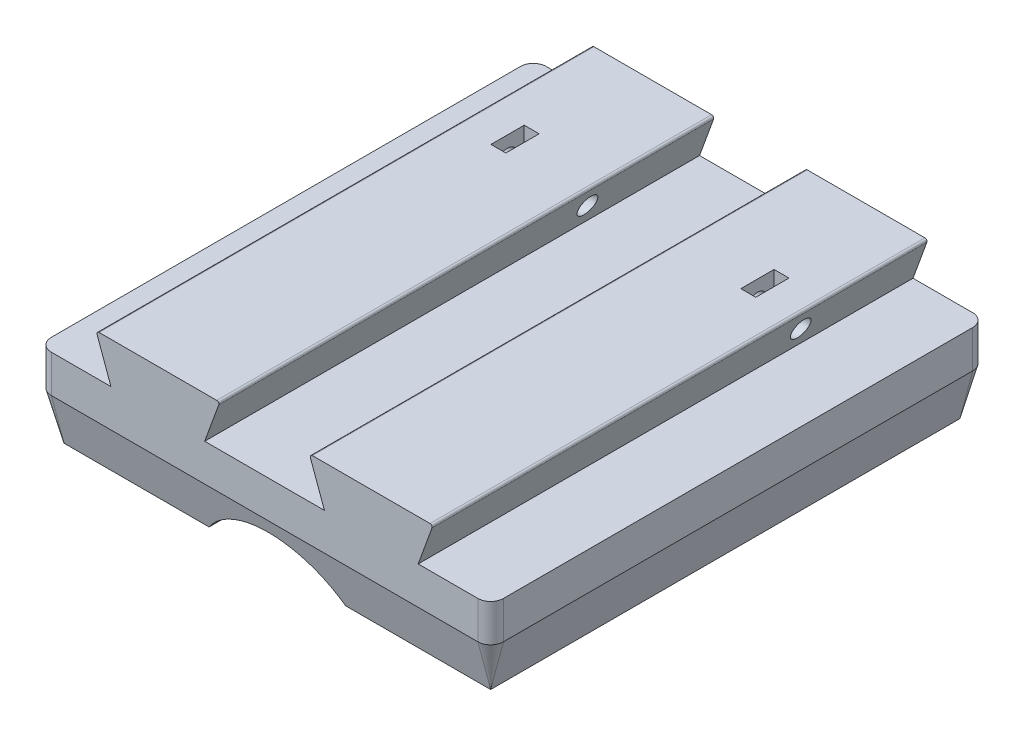
SolidWorks part; units mm, degrees
ref_plane "Front Plane" through (0, 0, 0) normal (0, 0, 1) x (1, 0, 0)
ref_plane "Top Plane" through (0, 0, 0) normal (0, 1, 0) x (1, 0, 0)
ref_plane "Right Plane" through (0, 0, 0) normal (1, 0, 0) x (0, 0, -1)
sketch "Sketch2" plane through (0, 0, 0) normal (0, 0, 1) x (1, 0, 0)
  line L0 (-39.5, -5.2867) -> (-10.5, -5.2867)
  line L1 (-10.5, -5.2867) -> (-14.0354, -15)
  line L2 (-14.0354, -15) -> (14.0354, -15)
  line L4 (-36.0059, -14.8867) -> (-39.5, -5.2867)
  line L5 (0, -16.28) -> (0, 16.28) construction
  line L10 (-36.0059, -14.8867) -> (-53, -14.8867)
  line L11 (-53, -14.8867) -> (-53, -34.8867)
  line L12 (-53, -34.8867) -> (-16, -34.8867)
  line L13 (39.5, -5.2867) -> (10.5, -5.2867)
  line L14 (10.5, -5.2867) -> (14.0354, -15)
  line L15 (53, -34.8867) -> (16, -34.8867)
  line L16 (53, -14.8867) -> (53, -34.8867)
  line L17 (36.0059, -14.8867) -> (53, -14.8867)
  line L18 (36.0059, -14.8867) -> (39.5, -5.2867)
  arc A0 (16, -34.8867) -> (-16, -34.8867) centre (0, -46.8867) ccw
  point P7 (-25, -5.2867)
  point P16 (0, -15)
  dimension "D5" = 40
  dimension "D1" = 25
  dimension "D2" = 29
  dimension "D3" = 20
  dimension "D4" = 12
  dimension "D6" = 53
  dimension "D7" = 70
  dimension "D8" = 70
  dimension "D9" = 9.6
extrude "Boss-Extrude1" add sketch "Sketch2" along normal blind 116 contours L15 A0 L12 L11 L10 L4 L0 L1 L2 L14 L13 L18 L17 L16
fillet "Fillet1" radius 3 4 edges at (53, -24.8867, 116) (-53, -24.8867, 116) (-53, -24.8867, 0) (53, -24.8867, 0)
chamfer "Chamfer2" distance 3 angle 75 5 edges at (52.1213, -34.8867, 0.8787) (-33, -34.8867, 0) (-52.1213, -34.8867, 115.1213) (-53, -34.8867, 58) (33, -34.8867, 116) tangent propagation no first distance on face at (39.8738, -34.8867, 58) first distance on face at (-39.8738, -34.8867, 58)
fillet "Fillet2" radius 0.5 4 edges at (-39.5, -5.2867, 58) (-10.5, -5.2867, 58) (10.5, -5.2867, 58) (39.5, -5.2867, 58)
sketch "Sketch3" plane through (0, -5.2867, 0) normal (0, 1, 0) x (1, 0, 0)
  line L0 (-38.7859, 0) -> (-11.2141, 0) construction
  line L1 (-31.0359, -24.1) -> (-27.5359, -24.1)
  line L2 (-31.0359, -24.1) -> (-31.0359, -31.9)
  line L3 (-31.0359, -31.9) -> (-27.5359, -31.9)
  line L4 (-27.5359, -24.1) -> (-27.5359, -31.9)
  line L5 (-31.0359, -24.1) -> (-27.5359, -31.9) construction
  line L6 (-31.0359, -31.9) -> (-27.5359, -24.1) construction
  line L7 (0, -16.28) -> (0, 16.28) construction
  line L8 (31.0359, -31.9) -> (27.5359, -24.1) construction
  line L9 (31.0359, -24.1) -> (27.5359, -31.9) construction
  line L10 (27.5359, -24.1) -> (27.5359, -31.9)
  line L11 (31.0359, -31.9) -> (27.5359, -31.9)
  line L12 (31.0359, -24.1) -> (31.0359, -31.9)
  line L13 (31.0359, -24.1) -> (27.5359, -24.1)
  line L14 (-39.2859, 0) -> (-39.2859, -116) construction
  point P0 (-29.2859, -28)
  point P6 (0, 0)
  point P15 (25, 0)
  point P16 (29.2859, -28)
  point P17 (0, 0)
  dimension "D1" = 7.8
  dimension "D2" = 3.5
  dimension "D3" = 28
  dimension "D4" = 10
extrude "Cut-Extrude1" cut sketch "Sketch3" against normal blind 9
sketch "Sketch4" plane through (-53, 0, 0) normal (-1, 0, 0) x (0, 0, 1)
  line L0 (0, -5.2867) -> (116, -5.2867) construction
  line L1 (0, -14.8867) -> (0, -5.9577) construction
  circle A0 centre (28, -10.2867) radius 2.3
  dimension "D1" = 5
  dimension "D2" = 4.6
  dimension "D3" = 28
extrude "Cut-Extrude2" cut sketch "Sketch4" against normal through all
sketch "Sketch5" plane through (0, 0, 0) normal (0, 0, -1) x (-1, 0, 0)
  circle A0 centre (0, -46.8867) radius 20
  circle A1 centre (0, -46.8867) radius 25
  circle A2 centre (0, -46.8867) radius 30
  line M14 (-50, -23.6905) -> (50, -23.6905)
  dimension "D1" = 5
  dimension "D2" = 5
extrude "Cut-Extrude3" cut sketch "Sketch5" against normal blind 22 from offset 20 contours A2 A1 M14 | A2 A1 M14 region at (-21.3779, -32.4395, 0) region at (0, -20.6441, 0) offset against normal yes
extrude "Cut-Extrude4" cut sketch "Sketch5<3>" along normal blind 22 from offset 96 contours A2 A1 M14 | A2 A1 M14 region at (-21.3779, -32.4395, 0) region at (0, -20.6441, 0) offset against normal yes
sketch "Sketch5<3>" plane through (0, 0, 0) normal (0, 0, -1) x (-1, 0, 0) same geometry as "Sketch5"
